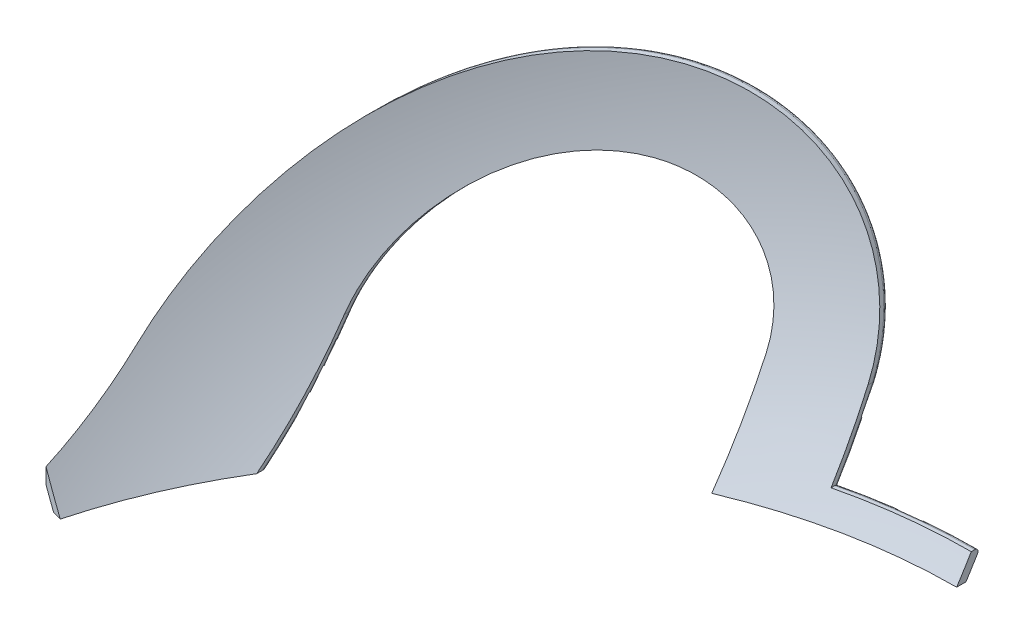
SolidWorks part; units mm, degrees
ref_plane "Front Plane" through (0, 0, 0) normal (0, 0, 1) x (1, 0, 0)
ref_plane "Top Plane" through (0, 0, 0) normal (0, 1, 0) x (1, 0, 0)
ref_plane "Right Plane" through (0, 0, 0) normal (1, 0, 0) x (0, 0, -1)
sketch "Sketch1" plane through (0, 0, 0) normal (1, 0, 0) x (0, 0, -1)
  line L0 (230.505, -11.7951) -> (234.2861, -11.7951)
  line L1 (271.7216, 121.5549) -> (274.8974, 121.5549)
  line L2 (224.3503, -11.7951) -> (230.505, -11.7951) construction
  line L4 (17.78, 127) -> (17.78, 273.6933) construction
  line L5 (0, 107.5849) -> (0, 26.3049) construction
  line L6 (0, 107.5849) -> (0, 26.3049) construction
  arc A0 (230.505, -11.7951) -> (271.7216, 121.5549) centre (17.78, 127) ccw
  arc A1 (240.6891, 5.2316) -> (254.3432, 34.513) centre (17.78, 127) ccw construction
  arc A3 (234.2861, -11.7951) -> (274.8974, 121.5549) centre (17.78, 127) ccw
  arc A4 (258.4474, 45.7893) -> (266.8095, 76.9968) centre (17.78, 127) ccw construction
  circle A5 centre (17.78, 127) radius 257.175 construction
  circle A6 centre (17.78, 127) radius 254 construction
  point P1 (0, 83.4549)
  dimension "D2" = 38.1
  dimension "D3" = 57.15
  dimension "D1" = 3.175
revolve "Revolve1" add sketch "Sketch1" angle 75 about L4 reverse direction yes
sketch "Sketch2" plane through (0, 0, 0) normal (0, 0, 1) x (1, 0, 0)
  line L10 (248.3563, 121.5549) -> (0, 121.5549)
  line L11 (0, -11.7951) -> (209.1289, -11.7951)
  line L12 (248.3563, 121.5549) -> (0, 121.5549)
  line L13 (0, -11.7951) -> (209.1289, -11.7951)
  line L16 (50.8, -2.2701) -> (-50.8, -2.2701)
  line L17 (0, -11.7951) -> (209.1289, -11.7951) construction
  line L19 (-99.06, -49.8951) -> (-99.06, 26.3049)
  line L20 (-175.26, 26.3049) -> (-175.26, -49.8951)
  line L21 (0, 121.5549) -> (0, -11.7951)
  line L22 (0, 121.5549) -> (0, -11.7951)
  line L23 (-99.06, -49.8951) -> (-99.06, 26.3049)
  line L24 (-175.26, 26.3049) -> (-175.26, -49.8951)
  line L29 (50.8, 26.3049) -> (50.8, -49.8951)
  line L30 (213.36, -49.8951) -> (213.36, 26.3049)
  line L31 (50.8, 26.3049) -> (50.8, -49.8951)
  line L32 (213.36, -49.8951) -> (213.36, 26.3049)
  line L33 (-50.8, -49.8951) -> (-50.8, 26.3049)
  line L34 (-213.36, 26.3049) -> (-213.36, -49.8951)
  line L35 (-50.8, -49.8951) -> (-50.8, 26.3049)
  line L36 (-213.36, 26.3049) -> (-213.36, -49.8951)
  line L51 (82.55, 26.3049) -> (82.55, -49.8951)
  line L52 (181.61, -49.8951) -> (181.61, 26.3049)
  arc A13 (-99.06, 26.3049) -> (-175.26, 26.3049) centre (-137.16, 26.3049) ccw
  arc A14 (-175.26, -49.8951) -> (-99.06, -49.8951) centre (-137.16, -49.8951) ccw
  arc A15 (-99.06, 26.3049) -> (-175.26, 26.3049) centre (-137.16, 26.3049) ccw
  arc A16 (-175.26, -49.8951) -> (-99.06, -49.8951) centre (-137.16, -49.8951) ccw
  arc A21 (213.36, 26.3049) -> (50.8, 26.3049) centre (132.08, 26.3049) ccw
  arc A22 (50.8, -49.8951) -> (213.36, -49.8951) centre (132.08, -49.8951) ccw
  arc A23 (213.36, 26.3049) -> (50.8, 26.3049) centre (132.08, 26.3049) ccw
  arc A24 (50.8, -49.8951) -> (213.36, -49.8951) centre (132.08, -49.8951) ccw
  arc A25 (-50.8, 26.3049) -> (-213.36, 26.3049) centre (-132.08, 26.3049) ccw
  arc A26 (-213.36, -49.8951) -> (-50.8, -49.8951) centre (-132.08, -49.8951) ccw
  arc A27 (-50.8, 26.3049) -> (-213.36, 26.3049) centre (-132.08, 26.3049) ccw
  arc A28 (-213.36, -49.8951) -> (-50.8, -49.8951) centre (-132.08, -49.8951) ccw
  arc A43 (82.55, -49.8951) -> (181.61, -49.8951) centre (132.08, -49.8951) ccw
  arc A44 (181.61, 26.3049) -> (82.55, 26.3049) centre (132.08, 26.3049) ccw
  ellipse E3 centre (0, 127) end of major axis (0, -130.175) minor radius 248.412 (209.1289, -11.7951) -> (248.3563, 121.5549) ccw
  ellipse E5 centre (0, 127) end of major axis (0, -130.175) minor radius 248.412 (209.1289, -11.7951) -> (248.3563, 121.5549) ccw
  dimension "D3" = 9.525
  dimension "D1" = 0
  dimension "D2" = 0
  dimension "D4" = 31.75
  dimension "D5" = 0
  dimension "D6" = 0
extrude "Cut-Extrude1" cut sketch "Sketch2" against normal through all contours L52 A44 L51 L13 | L13 E5 L12 L22 L16 L31 A23 L32 region at (236.1313, 56.9557, 0) region at (132.08, 27.4989, 0)
fillet "Fillet1" radius 1.27 7 edges at (25.5697, -2.2701, -238.6293) (213.36, 8.6202, -99.0371) (120.9694, 106.822, -243.8292) (50.8, 11.7833, -242.0197) (82.55, 6.7677, -229.6023) (115.0478, 72.8143, -241.3127) (181.61, 6.0649, -153.9104)
mirror "Mirror1" about plane through (0, 127, -17.78) normal (1, 0, 0) of bodies 105
delete or keep bodies "Body-Delete/Keep 1" type delete bodies bodies 105
